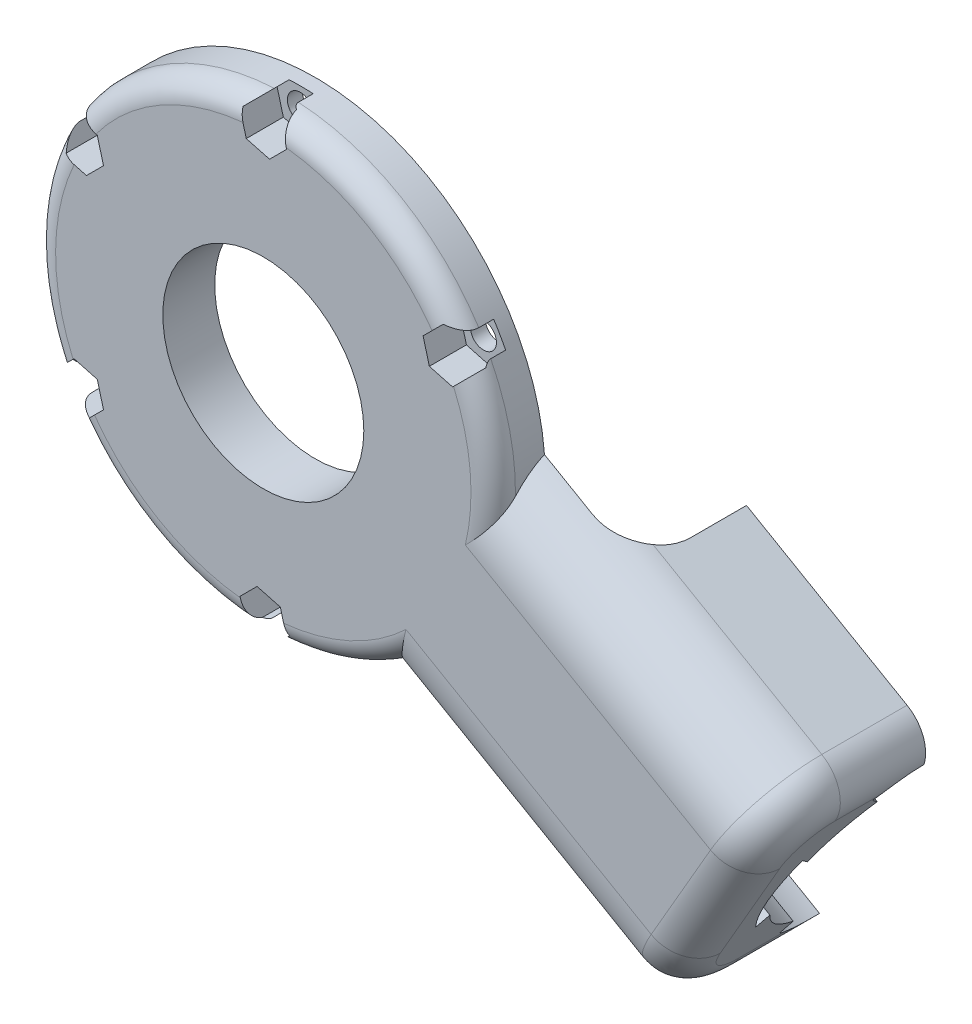
SolidWorks part; units mm, degrees
note: '?' marks a value the reader was unsure of.
ref_plane "Front Plane" through (0, 0, 0) normal (0, 0, 1) x (1, 0, 0)
ref_plane "Top Plane" through (0, 0, 0) normal (0, 1, 0) x (1, 0, 0)
ref_plane "Right Plane" through (0, 0, 0) normal (1, 0, 0) x (0, 0, -1)
sketch "Sketch2" plane through (0, 0, 0) normal (0, 0, 1) x (1, 0, 0)
  line L25 (-1.9398, -4.7631) -> (-17.4398, -31.6099) construction
  line L26 (-1.9398, -4.7631) -> (13.5602, 22.0836) construction
  line L27 (-17.4398, -31.6099) -> (43.182, -66.6099)
  line L28 (43.182, -66.6099) -> (74.182, -12.9164)
  line L29 (-1.9398, -4.7631) -> (4.8352, 6.9715) construction
  line L30 (13.5602, 22.0836) -> (74.182, -12.9164)
  line L56 (13.5602, 22.0836) -> (31.8352, 53.7369) construction
  arc A39 (13.5602, 22.0836) -> (-17.4398, -31.6099) centre (-1.9398, -4.7631) ccw
  circle A55 centre (-1.9398, -4.7631) radius 13.55
  point P59 (0.8102, 0)
  point P62 (-0.1961, -0.0206)
  dimension "D1" = 70
  dimension "D3" = 27.1
  dimension "D4" = 31
extrude "Boss-Extrude2" add sketch "Sketch2" along normal blind 7
sketch "Sketch4" plane through (0, 0, 0) normal (0, 0, -1) x (-1, 0, 0)
  line L6 (-74.182, -12.9164) -> (-43.182, -66.6099)
  line L7 (-43.182, -66.6099) -> (-17.2012, -51.6099)
  line L8 (17.4398, -31.6099) -> (-43.182, -66.6099) construction
  line L9 (-17.2012, -51.6099) -> (-48.2012, 2.0836)
  line L10 (-13.5602, 22.0836) -> (-74.182, -12.9164) construction
  line L11 (-48.2012, 2.0836) -> (-74.182, -12.9164)
  dimension "D1" = 30
extrude "Boss-Extrude4" add sketch "Sketch4" along normal blind 14.5 contours L9 L11 L6 L7
sketch "Sketch5" plane through (0, 0, 7) normal (0, 0, 1) x (1, 0, 0)
  line L0 (-1.9398, -4.7631) -> (13.5602, 22.0836) construction
  line L1 (-1.9398, -4.7631) -> (-17.4398, -31.6099) construction
  line L2 (-1.9398, -4.7631) -> (58.682, -39.7631) construction
  line L3 (43.182, -66.6099) -> (74.182, -12.9164) construction
  line L4 (35.3262, -47.0633) -> (49.682, -55.3516)
  line L5 (35.3262, -47.0633) -> (10.9177, -32.971)
  line L6 (53.3262, -15.8864) -> (59.8262, -4.628) construction
  line L10 (74.182, -12.9164) -> (13.5602, 22.0836)
  line L11 (-17.4398, -31.6099) -> (43.182, -66.6099)
  line L12 (43.182, -66.6099) -> (74.182, -12.9164)
  line L13 (74.182, -12.9164) -> (13.5602, 22.0836)
  line L14 (-17.4398, -31.6099) -> (43.182, -66.6099)
  line L15 (43.182, -66.6099) -> (74.182, -12.9164)
  line L16 (35.3262, -47.0633) -> (28.8262, -58.3216) construction
  line L17 (53.3262, -15.8864) -> (67.682, -24.1747)
  line L18 (53.3262, -15.8864) -> (28.9177, -1.7941)
  arc A1 (-17.4398, -31.6099) -> (13.5602, 22.0836) centre (-1.9398, -4.7631) ccw
  arc A3 (13.5602, 22.0836) -> (-17.4398, -31.6099) centre (-1.9398, -4.7631) ccw
  dimension "D1" = 0
  dimension "D2" = 13
extrude "Cut-Extrude1" cut sketch "Sketch5" against normal blind 25
sketch "Sketch6" plane through (61.2295, -35.3508, 0) normal (0.866, -0.5, 0) x (0, 0, -1)
  line L8 (3.1693, -0.0166) -> (1.8927, 1.26)
  line L9 (1.8927, -11.368) -> (3.1693, -10.0914)
  line L10 (9.4626, -16.3847) -> (8.186, -17.6613)
  line L11 (20.814, -17.6613) -> (19.5374, -16.3847)
  line L12 (25.8307, -10.0914) -> (27.1073, -11.368)
  line L13 (27.1073, 1.26) -> (25.8307, -0.0166)
  line L14 (19.5374, 6.2767) -> (20.814, 7.5533)
  line L15 (8.186, 7.5533) -> (9.4626, 6.2767)
  line L16 (14.5, -5.054) -> (14.5, 12.9051) construction
  arc A9 (1.8927, 1.26) -> (1.8927, -11.368) centre (14.5, -5.054) ccw
  arc A10 (3.1693, -10.0914) -> (9.4626, -16.3847) centre (14.5, -5.054) ccw
  arc A11 (8.186, -17.6613) -> (20.814, -17.6613) centre (14.5, -5.054) ccw
  arc A12 (19.5374, -16.3847) -> (25.8307, -10.0914) centre (14.5, -5.054) ccw
  arc A13 (27.1073, -11.368) -> (28.6, -5.054) centre (14.5, -5.054) ccw
  arc A14 (28.6, -5.054) -> (27.1073, 1.26) centre (14.5, -5.054) ccw
  arc A15 (25.8307, -0.0166) -> (19.5374, 6.2767) centre (14.5, -5.054) ccw
  arc A16 (20.814, 7.5533) -> (8.186, 7.5533) centre (14.5, -5.054) ccw
  arc A17 (9.4626, 6.2767) -> (3.1693, -0.0166) centre (14.5, -5.054) ccw
  point P4 (15, 0.4051)
  dimension "D1" = 12.4
  dimension "D2" = 14.1
extrude "Cut-Extrude2" cut sketch "Sketch6" against normal blind 25
ref_axis "Axis1" through (-1.9398, -4.7631, 7) along (0, 0, -1)?
fillet "Fillet1" radius 7 1 edges at (32.7012, -24.7631, 0)
fillet "Fillet4" radius 3 1 edges at (-28.7866, 10.7369, 7)
fillet "Fillet5" radius 10 2 edges at (46.6582, -12.0366, 7) (28.6582, -43.2135, 7)
fillet "Fillet6" radius 5 5 edges at (67.682, -24.1747, -8.75) (66.2175, -26.7112, 4.0711) (58.682, -39.7631, 7) (49.682, -55.3516, -8.75) (51.1465, -52.8151, 4.0711)
ref_plane "Plane1" through (-2.5474, -4.4123, 0) normal (-0.5, -0.866, 0) x (-0.866, 0.5, 0)
ref_axis "Axis2" through (21.7457, -18.4379, 7) along (0.866, -0.5, 0)?
sketch "Sketch9" plane through (0, 0, 7) normal (0, 0, 1) x (1, 0, 0)
  line L0 (-1.9398, -4.7631) -> (22.742, 9.4869) construction
  line L2 (-26.2979, 9.3) -> (21.203, -18.1246) construction
  circle A0 centre (22.742, 9.4869) radius 1.75
  dimension "D2" = 3.5
  dimension "D3" = 60
  dimension "D1" = 28.5
extrude "Cut-Extrude5" cut sketch "Sketch9" against normal blind 10
sketch "Sketch11" plane through (0, 0, 7) normal (0, 0, 1) x (1, 0, 0)
  line L0 (-1.9398, -4.7631) -> (22.742, 9.4869) construction
  line L1 (-1.9398, -4.7631) -> (22.742, 9.4869) construction
  line L9 (20.4439, 7.1888) -> (23.5831, 6.3476)
  line L10 (23.5831, 6.3476) -> (25.8812, 8.6457)
  line L11 (25.8812, 8.6457) -> (25.0401, 11.785)
  line L12 (25.0401, 11.785) -> (21.9008, 12.6261)
  line L13 (21.9008, 12.6261) -> (19.6027, 10.328)
  line L14 (19.6027, 10.328) -> (20.4439, 7.1888)
  circle A1 centre (22.742, 9.4869) radius 2.8146 construction
  dimension "D2" = 28.5
  dimension "D3" = 0
  dimension "D4" = 6.5
extrude "Cut-Extrude6" cut sketch "Sketch11" against normal blind 5
pattern_circular "CirPattern3" count 5 every 60 about axis through (-1.9398, -4.7631, 0) along (0, 0, 1) of "Cut-Extrude5", "Cut-Extrude6"
